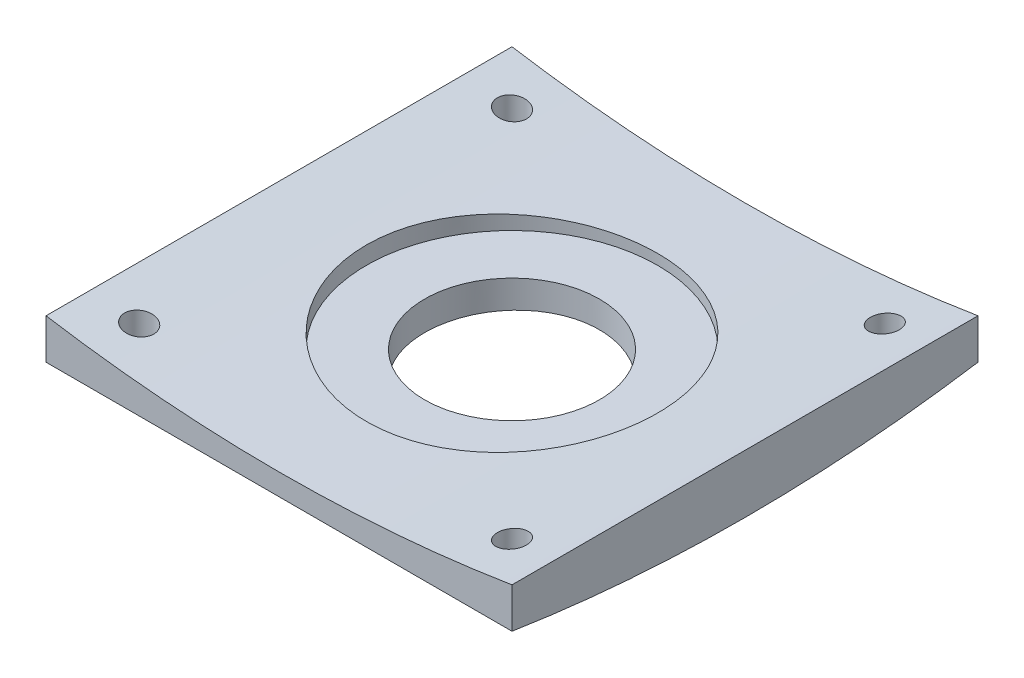
SolidWorks part; units mm, degrees
ref_plane "Front Plane" through (0, 0, 0) normal (0, 0, 1) x (1, 0, 0)
ref_plane "Top Plane" through (0, 0, 0) normal (0, 1, 0) x (1, 0, 0)
ref_plane "Right Plane" through (0, 0, 0) normal (1, 0, 0) x (0, 0, -1)
sketch "Sketch1" plane through (0, 0, 0) normal (0, 1, 0) x (1, 0, 0)
  line L1 (-40, -40) -> (40, -40)
  line L2 (-40, -40) -> (-40, 40)
  line L3 (-40, 40) -> (40, 40)
  line L4 (40, -40) -> (40, 40)
  line L5 (-40, -40) -> (40, 40) construction
  line L6 (-40, 40) -> (40, -40) construction
  circle A0 centre (0, 0) radius 15
  circle A1 centre (0, 0) radius 25
  circle A2 centre (-32, 32) radius 2.5
  circle A3 centre (-32, -32) radius 2.5
  circle A4 centre (32, -32) radius 2.5
  circle A5 centre (32, 32) radius 2.5
  point P19 (0, 0)
  dimension "D1" = 50
  dimension "D2" = 30
  dimension "D4" = 5
  dimension "D3" = 80
  dimension "D5" = 8
  dimension "D6" = 4
extrude "Boss-Extrude3" add sketch "Sketch1<3>" against normal blind 5 contours L1 L4 L3 L2 A1 | A1 A0 region at (-38.8686, 0, 0) region at (-24.2929, 0, 0)
sketch "Sketch1<3>" plane through (0, 0, 0) normal (0, 1, 0) x (1, 0, 0) same geometry as "Sketch1"
extrude "Boss-Extrude4" add sketch "Sketch1" along normal blind 5 contours L1 L4 L3 L2 A1 region at (-38.8686, 0, 0)
sketch "Sketch5" plane through (0, 0, -40) normal (0, 0, -1) x (-1, 0, 0)
  line L0 (40, 5) -> (-40, 5)
  arc A0 (40, 5) -> (-40, 5) centre (0, 251.7793) cw
  dimension "D1" = 250
extrude "Cut-Extrude1" cut sketch "Sketch5" against normal through all
sketch "Sketch7" plane through (40, 0, 0) normal (1, 0, 0) x (0, 0, -1)
  line L0 (40, -5) -> (40, 5) construction
  line L1 (-40, -5) -> (-40, 5) construction
  line L2 (0, -5) -> (0, 255) construction
  line L3 (-40, -5) -> (40, -5) construction
  line L4 (-40, -1.9047) -> (-40, -5)
  line L5 (-40, -5) -> (0, -5)
  line L6 (0, -5) -> (40, -5)
  line L7 (40, -5) -> (40, -1.9047)
  arc A0 (40, -1.9047) -> (-40, -1.9047) centre (0, 255) cw
  dimension "D1" = 260
extrude "Cut-Extrude2" cut sketch "Sketch7" against normal through all contours L2 A0 region at (40, -4.0724, 30.0119)
extrude "Cut-Extrude3" cut sketch "Sketch7<3>" against normal through all contours A0 L2 region at (40, -4.0724, -30.0119)
sketch "Sketch7<3>" plane through (40, 0, 0) normal (1, 0, 0) x (0, 0, -1) same geometry as "Sketch7"
